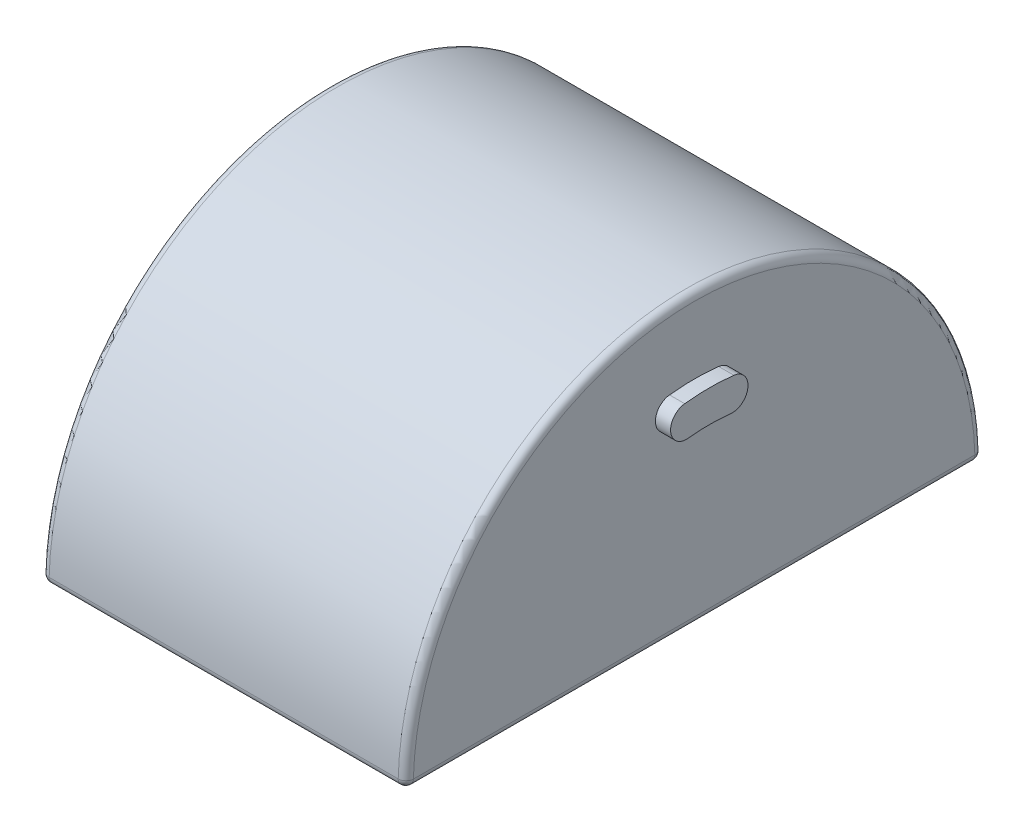
SolidWorks part; units mm, degrees
ref_plane "Front Plane" through (0, 0, 0) normal (0, 0, 1) x (1, 0, 0)
ref_plane "Top Plane" through (0, 0, 0) normal (0, 1, 0) x (1, 0, 0)
ref_plane "Right Plane" through (0, 0, 0) normal (1, 0, 0) x (0, 0, -1)
sketch "Sketch5" plane through (0, 0, 0) normal (0, 0, 1) x (1, 0, 0)
  line L0 (-13.97, 0) -> (13.97, 0)
  arc A0 (11.176, 0) -> (-11.176, 0) centre (0, 0) ccw
  arc A1 (12.7, 0) -> (-12.7, 0) centre (0, 0) ccw
  arc A2 (13.97, 0) -> (-13.97, 0) centre (0, 0) ccw
  arc A3 (12.446, 0) -> (-12.446, 0) centre (0, 0) ccw
  arc A4 (8.636, 0) -> (-8.636, 0) centre (0, 0) ccw
  dimension "D1" = 24.892
  dimension "D2" = 25.4
  dimension "D3" = 27.94
  dimension "D4" = 22.352
  dimension "D5" = 17.272
sketch "Sketch6" plane through (0, 0, 0) normal (1, 0, 0) x (0, 0, -1)
  line L0 (0, 16.5466) -> (1.905, 16.5466)
  line L1 (0, 16.5466) -> (-1.905, 16.5466)
  line L2 (0, 15.2131) -> (0, 0) construction
  line L3 (-24.1384, 0) -> (24.3191, 0)
  line L8 (24.3191, 0) -> (-24.3191, 0) construction
  arc A1 (24.1384, 0) -> (-24.1384, 0) centre (0, 0) ccw
  arc A5 (18.1341, 0) -> (-18.1341, 0) centre (0, 0) ccw
  arc A6 (14.9591, 0) -> (-14.9591, 0) centre (0, 0) ccw
  arc A7 (17.8801, 0) -> (-17.8801, 0) centre (0, 0) ccw construction
  arc A8 (15.2131, 0) -> (-15.2131, 0) centre (0, 0) ccw construction
  circle A11 centre (0, 0) radius 16.5466 construction
  arc A12 (-1.905, 16.4366) -> (1.905, 16.4366) centre (0, 0) cw construction
  arc A22 (2.0585, 17.7612) -> (-2.0585, 17.7612) centre (0, 0) ccw
  arc A23 (1.7515, 15.1119) -> (-1.7515, 15.1119) centre (0, 0) ccw
  arc A24 (1.7515, 15.1119) -> (2.0585, 17.7612) centre (1.905, 16.4366) ccw
  arc A25 (-2.0585, 17.7612) -> (-1.7515, 15.1119) centre (-1.905, 16.4366) ccw
  point P24 (0, 16.5466)
  point P25 (0, 20.0109)
  dimension "D1" = 36.2682
  dimension "D2" = 29.9182
  dimension "D8" = 33.0932
  dimension "D7" = 15.2131
  dimension "D3" = 1.905
  dimension "D6" = 1.905
  dimension "D4" = 0.254
  dimension "D5" = 0.254
extrude "Main Body Extrude" add sketch "Sketch6" along normal mid plane 30.48 contours L8 A5 A7 | L8 A6 | L8 A8 A6 | L8 A7 A8 | L8 A1 A5 | A7 L3 A8 | A8 L3 A7 | A23 region at (0, 23.5986, 0) region at (0, 18.0936, 0) region at (0, 6.3488, 0)
extrude "Inner Hinge Cut" cut sketch "Sketch5<16>" against normal mid plane 30.48 contours L0 A2 A1 | L0 A3 A0 | A4 L0 A0 | L0 A4 | A3 L0 A1 region at (0, 13.6576, 0) region at (0, 12.6716, 0) region at (0, 12.1677, 0) region at (0, 10.9261, 0) region at (0, 3.6652, 0)
sketch "Sketch5<16>" plane through (0, 0, 0) normal (0, 0, 1) x (1, 0, 0) same geometry as "Sketch5"
extrude "Groove Cut" cut sketch "Sketch5" against normal mid plane 33.02 contours A4 L0 A0 region at (0, 10.9261, 0)
extrude "Slot 1 Extrude" add sketch "Sketch6<5>" along normal blind 1.27 from surface contours A22 A25 A23 A24 region at (0, 16.4839, 0) starting at face at (15.24, 16.4148, 0)
sketch "Sketch6<5>" plane through (0, 0, 0) normal (1, 0, 0) x (0, 0, -1) same geometry as "Sketch6"
extrude "Slot 2 Extrude" add sketch "Sketch6<6>" against normal blind 1.27 from surface contours L8 A7 A8 | A22 A25 A23 A24 region at (0, 16.4839, 0) starting at face at (-15.24, 16.4148, 0)
sketch "Sketch6<6>" plane through (0, 0, 0) normal (1, 0, 0) x (0, 0, -1) same geometry as "Sketch6"
fillet "Fillet1" radius 0.635 6 edges at (0, 0, -24.1384) (-15.24, 24.1384, 0) (-15.24, 0, 0) (15.24, 24.1384, 0) (15.24, 0, 0) (0, 0, 24.1384)
equation "\"InnerBaseDiameter\"=0.98"
equation "\"D1@Sketch5\"=\"InnerBaseDiameter\""
equation "\"InnerBaseOuterGroove\"= \"InnerBaseDiameter\" - 0.1"
equation "\"InnerHingeInnerCurve\"= 1"
equation "\"InnerHingeOuterCurve\" = \"InnerHingeInnerCurve\" + 0.1"
equation "\"InnerBaseInnerGroove\"= \"InnerBaseOuterGroove\" - 0.2"
equation "\"InnerHingeWidth\"= 1.45"
equation "\"OuterBaseInnerGroove\"= \"OuterBaseOuterGroove\" - 0.25"
equation "\"OuterBaseDiameter\"= ( ( \"InnerHingeOuterCurve\" / 2 ) ^ 2 + ( \"InnerHingeLength\" / 2 ) ^ 2 ) ^ 0.5 * 2"
equation "\"InnerHingeLength\"=1.2"
equation "\"OuterBaseOuterGroove\" = \"OuterBaseDiameter\" - 0.2"
equation "\"D1@Sketch6\"=\"OuterBaseOuterGroove\""
equation "\"D2@Sketch6\"=\"OuterBaseInnerGroove\""
equation "\"D1@Main Body Extrude\" = \"InnerHingeOuterCurve\" + 0.1"
equation "\"D4@Sketch5\"=\"InnerBaseOuterGroove\""
equation "\"D5@Sketch5\"=\"InnerBaseInnerGroove\""
equation "\"D8@Sketch6\"=\"OuterBaseInnerGroove\" * 0.5 + \"OuterBaseOuterGroove\"*0.5"
equation "\"D7@Sketch6\"=\"OuterBaseInnerGroove\" * 0.5+0.01"
